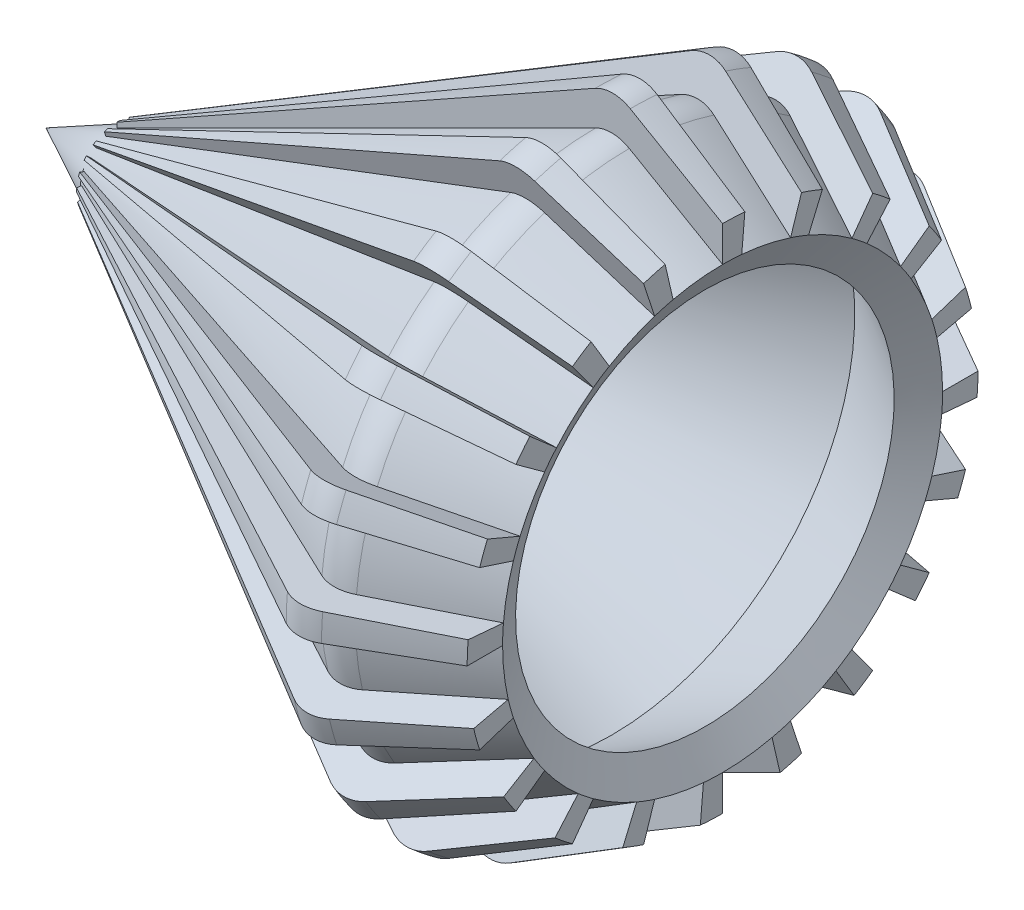
SolidWorks part; units mm, degrees
ref_plane "Front Plane" through (0, 0, 0) normal (0, 0, 1) x (1, 0, 0)
ref_plane "Top Plane" through (0, 0, 0) normal (0, 1, 0) x (1, 0, 0)
ref_plane "Right Plane" through (0, 0, 0) normal (1, 0, 0) x (0, 0, -1)
sketch "Sketch2" plane through (0, 0, 0) normal (0, 0, 1) x (1, 0, 0)
  line L0 (33.4615, 0) -> (-190.5, 0) construction
  line L1 (-190.5, 0) -> (-263.4708, 0) construction
  line L5 (39.3699, 78.8698) -> (0, 101.6)
  line L6 (0, 101.6) -> (-203.2, 0)
  line L8 (33.0199, 67.8713) -> (-0.4322, 87.1849)
  line L9 (-0.4322, 87.1849) -> (-174.8019, 0)
  line L10 (-203.2, 0) -> (-174.8019, 0)
  line L11 (-0.4322, 87.1849) -> (-197.5204, -11.3592) construction
  line L12 (39.3699, 78.8698) -> (33.0199, 67.8713)
  line L13 (0, 0) -> (0, 134.0479) construction
  dimension "D1" = 101.6
  dimension "D2" = 203.2
  dimension "D3" = 12.7
  dimension "D4" = 30
revolve "Revolve1" add sketch "Sketch2" angle 360 about L0
sketch "Sketch3" plane through (0, 0, 0) normal (0, 0, 1) x (1, 0, 0)
  line L0 (-177.8, 14.4619) -> (0, 114.3)
  line L1 (0, 114.3) -> (39.3699, 91.5698)
  line L2 (39.3699, 91.5698) -> (39.3699, 78.8698)
  line L3 (39.3699, 78.8698) -> (0, 101.6)
  line L4 (0, 101.6) -> (-177.8, 12.7)
  line L5 (0, 0) -> (0, 133.0618) construction
  line L6 (95.9453, 0) -> (-261.7553, 0) construction
  line L7 (-177.8, 14.4619) -> (-177.8, 12.7)
  line L8 (0, 101.6) -> (-203.2, 0) construction
  point P13 (-127, 38.1)
  dimension "D1" = 114.3
  dimension "D2" = 177.8
  dimension "D3" = 2.75
revolve "Revolve8" add sketch "Sketch3" angle 5 about L6
ref_axis "Axis1" through (-279.6403, 0, 0) along (1, 0, 0)
pattern_circular "CirPattern3" count 20 over 360 about axis through (-279.6403, 0, 0) along (1, 0, 0) of bodies 102
combine bodies "Combine1" bodies to combine 121 102 103 104 105 101 106 107 108 109 110 111 112 113 114 115 117 116 118 119 120
fillet "Fillet2" radius 12.7 40 edges at (0, 71.1534, 89.4521) (0, 50.0302, 88.4281) (0, 40.0287, 107.0616) (0, 20.2558, 99.5603) (0, 4.9857, 114.1912) (0, -11.5014, 100.9469) (0, -30.5453, 110.143) (0, -42.1328, 92.4521) (0, -63.0864, 95.3131) (0, -68.64, 74.9074) (0, -89.4521, 71.1534) (0, -88.4281, 50.0302) (0, -107.0616, 40.0287) (0, -99.5603, 20.2558) (0, -114.1912, 4.9857) (0, -100.9469, -11.5014) (0, -110.143, -30.5453) (0, -92.4521, -42.1328) (0, -95.3131, -63.0864) (0, -74.9074, -68.64) (0, -71.1534, -89.4521) (0, -50.0302, -88.4281) (0, -40.0287, -107.0616) (0, -20.2558, -99.5603) (0, -4.9857, -114.1912) (0, 11.5014, -100.9469) (0, 30.5453, -110.143) (0, 42.1328, -92.4521) (0, 63.0864, -95.3131) (0, 68.64, -74.9074) (0, 89.4521, -71.1534) (0, 88.4281, -50.0302) (0, 107.0616, -40.0287) (0, 99.5603, -20.2558) (0, 100.9469, 11.5014) (0, 92.4521, 42.1328) (0, 74.9074, 68.64) (0, 95.3131, 63.0864) (0, 110.143, 30.5453) (0, 114.1912, -4.9857)
